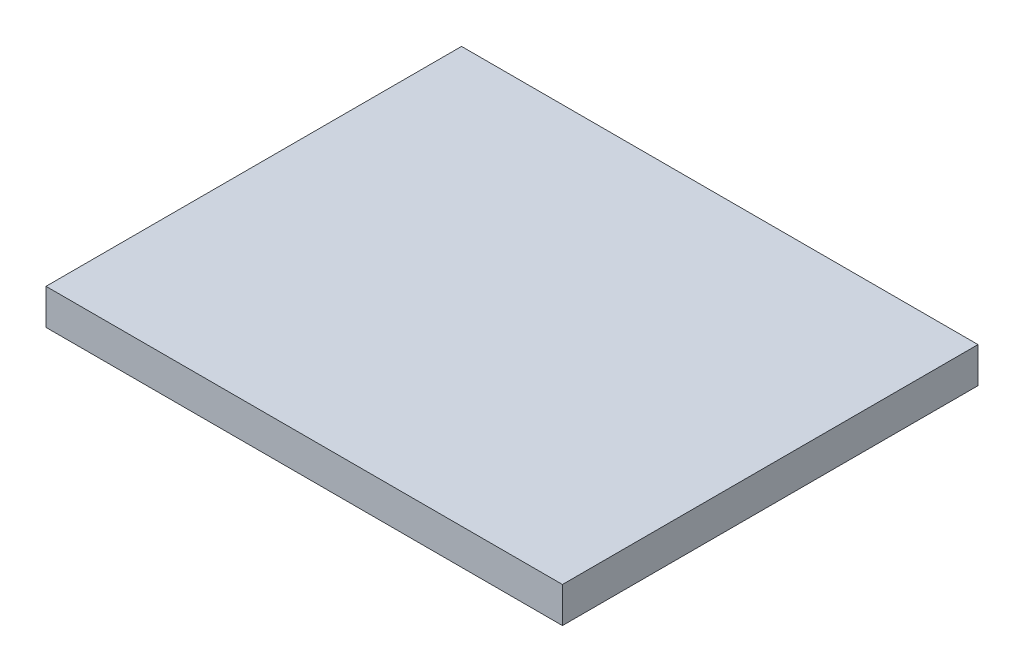
SolidWorks part; units mm, degrees
material "Acrylic (Medium-high impact)"
ref_plane "Front Plane" through (0, 0, 0) normal (0, 0, 1) x (1, 0, 0)
ref_plane "Top Plane" through (0, 0, 0) normal (0, 1, 0) x (1, 0, 0)
ref_plane "Right Plane" through (0, 0, 0) normal (1, 0, 0) x (0, 0, -1)
sketch "Sketch1" plane through (0, 0, 0) normal (0, 1, 0) x (1, 0, 0)
  line L0 (-102.9438, 52.5) -> (-102.9438, -17.5)
  line L1 (-189.9438, 52.5) -> (-102.9438, 52.5)
  line L2 (-189.9438, 52.5) -> (-189.9438, -17.5)
  line L3 (-189.9438, -17.5) -> (-102.9438, -17.5)
  dimension "D1" = 70
  dimension "D2" = 87
extrude "Boss-Extrude1" add sketch "Sketch1" along normal blind 6
